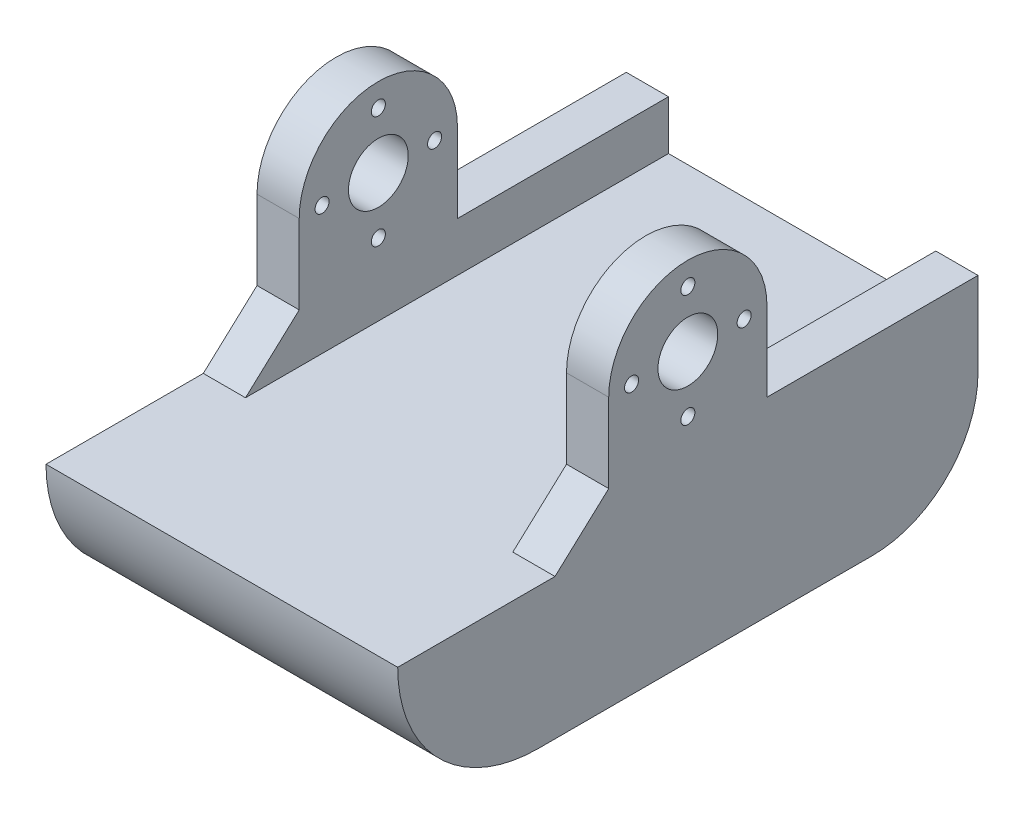
SolidWorks part; units mm, degrees
ref_plane "Front Plane" through (0, 0, 0) normal (0, 0, 1) x (1, 0, 0)
ref_plane "Top Plane" through (0, 0, 0) normal (0, 1, 0) x (1, 0, 0)
ref_plane "Right Plane" through (0, 0, 0) normal (1, 0, 0) x (0, 0, -1)
sketch "Sketch1" plane through (0, 0, 0) normal (0, 0, 1) x (1, 0, 0)
  line L1 (-25, 0) -> (25, 0)
  line L2 (-25, 0) -> (-25, -170)
  line L3 (-25, -170) -> (25, -170)
  line L4 (25, 0) -> (25, -170)
  dimension "D1" = 170
  dimension "D2" = 50
extrude "Boss-Extrude1" add sketch "Sketch1" against normal blind 55
sketch "Sketch2" plane through (0, 0, 0) normal (0, 0, 1) x (1, 0, 0)
  line L0 (25, 0) -> (-25, 0) construction
  line L1 (-17, 0) -> (17, 0)
  line L2 (-17, 0) -> (-17, -27)
  line L3 (-17, -27) -> (17, -27)
  line L4 (17, 0) -> (17, -27)
  line L5 (-25, 0) -> (-25, -170) construction
  dimension "D1" = 8
  dimension "D2" = 34
  dimension "D3" = 27
extrude "Cut-Extrude1" cut sketch "Sketch2" against normal through all
sketch "Sketch3" plane through (25, 0, 0) normal (1, 0, 0) x (0, 0, -1)
  line L0 (0, -170) -> (0, 0) construction
  line L1 (55, -27) -> (0, -27)
  line L2 (55, -27) -> (55, -24)
  line L3 (55, -24) -> (0, -24)
  line L4 (0, -27) -> (0, -24)
  line L5 (55, -170) -> (55, 0) construction
  line L7 (0, 0) -> (10, 0)
  line L8 (0, 0) -> (0, -24)
  line L9 (0, -24) -> (10, -24)
  line L10 (10, 0) -> (10, -24)
  line L11 (55, 0) -> (45, 0)
  line L12 (55, 0) -> (55, -24)
  line L13 (55, -24) -> (45, -24)
  line L14 (45, 0) -> (45, -24)
  circle A0 centre (27.5, -12.75) radius 10.25
  circle A1 centre (27.5, -12.75) radius 4.25
  circle A2 centre (27.5, -12.75) radius 8
  circle A3 centre (27.5, -4.75) radius 1
  circle A4 centre (35.5, -12.75) radius 1
  circle A5 centre (27.5, -20.75) radius 1
  circle A6 centre (19.5, -12.75) radius 1
  point P32 (27.5, -12.75)
  line M7 (0, 0) -> (0, -170)
  line M9 (55, -170) -> (55, 0)
  line M10 (55, 0) -> (0, 0)
  dimension "D2" = 11.25
  dimension "D3" = 27.5
  dimension "D4" = 20.5
  dimension "D7" = 8.5
  dimension "D8" = 16
  dimension "D9" = 4
  dimension "D1" = 3
  dimension "D5" = 10
  dimension "D6" = 10
extrude "Cut-Extrude2" cut sketch "Sketch3" against normal through all contours L14 L3 M10 M9 | L10 L3 M10 M7 | A2 A6 | A2 A6 | A1 | A2 A5 | A2 A5 | A2 A4 | A2 A4 | A2 A3 | A2 A3 region at (25, -12, -50) region at (25, -12, -5) region at (25, -12.75, -27.5) region at (25, -12.75, -35.0645) region at (25, -12.75, -35.913) region at (25, -5.1855, -27.5) region at (25, -4.337, -27.5) region at (25, -21.163, -27.5) region at (25, -20.3145, -27.5) region at (25, -12.75, -19.9355) region at (25, -12.75, -19.087)
sketch "Sketch4" plane through (0, 0, -10) normal (0, 0, 1) x (1, 0, 0)
  line L0 (-25, -24) -> (-17, -24) construction
  line L1 (-17, 0) -> (-19, 0)
  line L2 (-17, 0) -> (-17, -24)
  line L3 (-17, -24) -> (-19, -24)
  line L4 (-19, 0) -> (-19, -24)
  line L5 (0, 0) -> (0, -13.53) construction
  line L6 (19, 0) -> (19, -24)
  line L7 (17, -24) -> (19, -24)
  line L8 (17, 0) -> (17, -24)
  line L9 (17, 0) -> (19, 0)
  dimension "D1" = 2
extrude "Cut-Extrude3" cut sketch "Sketch4" against normal through all
sketch "Sketch5" plane through (25, 0, 0) normal (1, 0, 0) x (0, 0, -1)
  line L1 (10, 0) -> (45, 0)
  line L2 (10, 0) -> (10, -24)
  line L3 (10, -24) -> (45, -24)
  line L4 (45, 0) -> (45, -24)
  line L5 (38.75, -12.75) -> (38.75, -24)
  line L6 (16.25, -12.75) -> (10, -12.75)
  line L7 (16.25, -12.75) -> (16.25, -24)
  line L8 (16.25, -24) -> (10, -24)
  line L9 (10, -12.75) -> (10, -24)
  line L10 (38.75, -12.75) -> (45, -12.75)
  line L11 (38.75, -12.75) -> (38.75, -24)
  line L12 (38.75, -24) -> (45, -24)
  line L13 (45, -12.75) -> (45, -24)
  circle A0 centre (27.5, -12.75) radius 11.25
  line M8 (45, -24) -> (45, 0)
  line M9 (45, 0) -> (10, 0)
  line M10 (10, 0) -> (10, -24)
  dimension "D1" = 22.5
extrude "Cut-Extrude4" cut sketch "Sketch5" against normal through all contours A0 L10 L4 L6 M9 M10 | L7 L6 L2 L3 | L10 L5 L3 M8 region at (25, -0.3725, -27.5) region at (25, -18.375, -13.125) region at (25, -18.375, -41.875)
sketch "Sketch6" plane through (0, 0, 0) normal (0, 0, 1) x (1, 0, 0)
  line L1 (-19, -24) -> (19, -24)
  line L2 (-19, -24) -> (-19, -34)
  line L3 (-19, -34) -> (19, -34)
  line L4 (19, -24) -> (19, -34)
  dimension "D1" = 10
extrude "Cut-Extrude5" cut sketch "Sketch6" against normal through all
sketch "Sketch8" plane through (25, 0, 0) normal (1, 0, 0) x (0, 0, -1)
  line L0 (55, -170) -> (55, -24) construction
  line L1 (0, -170) -> (0, -24) construction
  line L2 (41.75, -132.5) -> (13.25, -132.5)
  line L3 (27.5, -132.5) -> (27.5, -179)
  line L4 (41.75, -179) -> (13.25, -179)
  line L5 (13.25, -132.5) -> (13.25, -179)
  line L7 (41.75, -132.5) -> (41.75, -179)
  line L11 (27.5, -167.75) -> (55, -167.75)
  line L12 (27.5, -167.75) -> (27.5, -170)
  line L13 (27.5, -170) -> (55, -170)
  line L14 (55, -167.75) -> (55, -170)
  line L16 (27.5, -167.75) -> (0, -167.75)
  line L17 (27.5, -167.75) -> (27.5, -170)
  line L18 (27.5, -170) -> (0, -170)
  line L19 (0, -167.75) -> (0, -170)
  circle A0 centre (27.5, -167.75) radius 10.25
  circle A1 centre (27.5, -12.75) radius 10.25
  line M4 (0, -24) -> (0, -170)
  line M5 (0, -170) -> (55, -170)
  line M6 (55, -170) -> (55, -24)
  dimension "D1" = 27.5
  dimension "D2" = 20.5
  dimension "D3" = 155
  dimension "D4" = 14.25
  dimension "D5" = 11.25
  dimension "D6" = 46.5
  dimension "D7" = 13.25
extrude "Cut-Extrude7" cut sketch "Sketch8" against normal through all contours A0 L3 L2 L5 L16 | A0 L11 L7 L2 L3 | L11 L7 M5 M6 | L5 L16 M4 M5 | A0 L16 L5 M5 | A0 L13 L7 L11 | L3 A0 L16 | L11 A0 L3 | L16 A0 L18 L3 | A0 L11 L3 M5 region at (25, -147.5157, -35.1704) region at (25, -147.5157, -19.8296) region at (25, -168.875, -48.375) region at (25, -168.8865, -39.7079) region at (25, -163.3998, -31.8502) region at (25, -163.3998, -23.1498) region at (25, -168.8704, -32.5838) region at (25, -168.8865, -15.2921) region at (25, -168.875, -6.625) region at (25, -168.8704, -22.4162)
sketch "Sketch9" plane through (0, 0, 0) normal (0, 0, 1) x (1, 0, 0)
  line L0 (-25, -167.75) -> (25, -167.75) construction
  line L1 (17, -167.75) -> (-17, -167.75)
  line L2 (17, -167.75) -> (17, -132.5)
  line L3 (17, -132.5) -> (-17, -132.5)
  line L4 (-17, -167.75) -> (-17, -132.5)
  line L5 (-25, -132.5) -> (25, -132.5) construction
  line L7 (-25, -24) -> (-25, -167.75) construction
  line L9 (25, -167.75) -> (25, -24) construction
  dimension "D1" = 8
  dimension "D2" = 8
extrude "Cut-Extrude8" cut sketch "Sketch9" against normal through all
sketch "Sketch11" plane through (25, 0, 0) normal (1, 0, 0) x (0, 0, -1)
  line L0 (27.5, -157.5) -> (27.5, -147.5)
  line L2 (27.5, -147.5) -> (55, -147.5)
  line L3 (27.5, -147.5) -> (27.5, -167.75)
  line L4 (27.5, -167.75) -> (55, -167.75)
  line L5 (55, -147.5) -> (55, -167.75)
  line L6 (27.5, -147.5) -> (0, -147.5)
  line L7 (27.5, -147.5) -> (27.5, -167.75)
  line L8 (27.5, -167.75) -> (0, -167.75)
  line L9 (0, -147.5) -> (0, -167.75)
  circle A0 centre (27.5, -167.75) radius 10.25
  arc A1 (38.75, -12.75) -> (16.25, -12.75) centre (27.5, -12.75) ccw construction
  line M1 (0, -167.75) -> (13.25, -167.75)
  line M2 (13.25, -167.75) -> (13.25, -132.5)
  line M4 (41.75, -132.5) -> (41.75, -167.75)
  line M5 (41.75, -167.75) -> (55, -167.75)
  line M6 (55, -167.75) -> (55, -24)
  line M12 (0, -24) -> (0, -167.75)
  dimension "D1" = 155
  dimension "D2" = 20.5
  dimension "D3" = 10
extrude "Cut-Extrude9" cut sketch "Sketch11" against normal through all contours A0 L0 L6 L8 M2 | A0 L4 L2 L0 M4 | L2 M4 M5 M6 | L6 M2 M12 M1 region at (25, -155.3124, -19.2638) region at (25, -155.3124, -35.7362) region at (25, -157.625, -48.375) region at (25, -157.625, -6.625)
sketch "Sketch12" plane through (25, 0, 0) normal (1, 0, 0) x (0, 0, -1)
  line L1 (13.25, -132.5) -> (41.75, -132.5)
  line L2 (13.25, -132.5) -> (13.25, -147.5)
  line L3 (13.25, -147.5) -> (41.75, -147.5)
  line L4 (41.75, -132.5) -> (41.75, -147.5)
extrude "Boss-Extrude2" add sketch "Sketch12" against normal blind 8
ref_plane "Plane1" through (0, 0, 0) normal (1, 0, 0) x (0, 0, -1)
mirror "Mirror1" about plane through (0, 0, 0) normal (1, 0, 0) of "Boss-Extrude2"
sketch "Sketch14" plane through (0, 0, 0) normal (0, 0, 1) x (1, 0, 0)
  line L0 (17, -148.55) -> (17, -158.75) construction
  line L1 (-17, -132.5) -> (17, -132.5)
  line L2 (-17, -132.5) -> (-17, -147.5)
  line L3 (-17, -147.5) -> (17, -147.5)
  line L4 (17, -132.5) -> (17, -147.5)
  line L5 (-17, -147.5) -> (17, -147.5)
  line L6 (-17, -147.5) -> (-17, -157.75)
  line L7 (-17, -157.75) -> (17, -157.75)
  line L8 (17, -147.5) -> (17, -157.75)
  line M11 (-17, -147.5) -> (-17, -132.5)
  line M12 (-17, -132.5) -> (17, -132.5)
  line M13 (17, -132.5) -> (17, -147.5)
  dimension "D1" = 10.25
extrude "Boss-Extrude3" add sketch "Sketch14" against normal blind 13.25 contours L3 M11 M13 M12 | L8 L3 L6 L7 region at (0, -140, 0) region at (0, -152.625, 0)
ref_plane "Plane2" through (0, 0, -27.5) normal (0, 0, 1) x (1, 0, 0)
mirror "Mirror2" about plane through (0, 0, -27.5) normal (0, 0, 1) of "Boss-Extrude3"
sketch "Sketch16" plane through (25, 0, 0) normal (1, 0, 0) x (0, 0, -1)
  line L0 (41.75, -132.5) -> (13.25, -132.5) construction
  line L1 (13.25, -132.5) -> (13.25, -147.5) construction
  circle A1 centre (16.5, -135.75) radius 2.5
  circle A2 centre (16.5, -135.75) radius 4.5
  circle A3 centre (38.5, -135.75) radius 4.5
  dimension "D1" = 3.25
  dimension "D2" = 3.25
  dimension "D3" = 2
extrude "Cut-Extrude13" cut sketch "Sketch16" against normal blind 8 contours A1 | A2 A1 | A3 region at (25, -135.75, -16.5) region at (25, -135.75, -12.1273) region at (25, -135.75, -38.5)
mirror "Mirror3" about plane through (0, 0, 0) normal (1, 0, 0) of "Cut-Extrude13"
sketch "Sketch17" plane through (25, 0, 0) normal (1, 0, 0) x (0, 0, -1)
  line L0 (55, -147.5) -> (55, -24) construction
  line L1 (27.5, -1.5) -> (55, -1.5)
  line L2 (27.5, -1.5) -> (27.5, -51.5)
  line L3 (27.5, -51.5) -> (55, -51.5)
  line L4 (55, -1.5) -> (55, -51.5)
  line L8 (55, -51.5) -> (0, -51.5)
  line L9 (55, -51.5) -> (55, -157.75)
  line L10 (55, -157.75) -> (0, -157.75)
  line L11 (0, -51.5) -> (0, -157.75)
  arc A0 (38.75, -12.75) -> (16.25, -12.75) centre (27.5, -12.75) ccw construction
  circle M2 centre (16.5, -135.75) radius 4.5
  circle M3 centre (38.5, -135.75) radius 4.5
  line M4 (0, -147.5) -> (55, -147.5)
  line M5 (55, -147.5) -> (55, -24)
  line M11 (0, -24) -> (0, -147.5)
  dimension "D1" = 50
extrude "Cut-Extrude15" cut sketch "Sketch17" against normal through all contours L3 L8 M11 M4 M5 M2 M3 | L11 L10 L9 M4 | M3 | M2 region at (25, -98.6049, -27.5) region at (25, -152.625, -27.5) region at (25, -135.75, -16.5) region at (25, -135.75, -38.5)
sketch "Sketch18" plane through (25, 0, 0) normal (1, 0, 0) x (0, 0, -1)
  line L1 (38.75, -24) -> (-71.25, -24)
  line L2 (38.75, -24) -> (38.75, -51.5)
  line L3 (38.75, -51.5) -> (-71.25, -51.5)
  line L4 (-71.25, -24) -> (-71.25, -51.5)
  line L6 (38.75, -24) -> (68.75, -24)
  line L7 (38.75, -24) -> (38.75, -51.5)
  line L8 (38.75, -51.5) -> (68.75, -51.5)
  line L9 (68.75, -24) -> (68.75, -51.5)
  line M8 (0, -24) -> (0, -51.5)
  line M9 (0, -51.5) -> (55, -51.5)
  line M10 (55, -51.5) -> (55, -24)
  line M11 (55, -24) -> (38.75, -24)
  line M15 (16.25, -24) -> (0, -24)
  dimension "D1" = 110
  dimension "D2" = 30
extrude "Boss-Extrude4" add sketch "Sketch18" against normal blind 50 contours L1 L4 L3 M8 | L9 L6 L8 M10 | L2 L1 M15 M8 M9 | L2 M11 M9 M10 region at (25, -37.75, -19.375) region at (25, -37.75, -46.875) region at (25, -37.75, -61.875) region at (25, -37.75, 35.625)
sketch "Sketch19" plane through (0, 0, 71.25) normal (0, 0, 1) x (1, 0, 0)
  line L1 (-19, -24) -> (19, -24)
  line L2 (-19, -24) -> (-19, -31)
  line L3 (-19, -31) -> (19, -31)
  line L4 (19, -24) -> (19, -31)
  dimension "D1" = 7
extrude "Cut-Extrude16" cut sketch "Sketch19" against normal through all
sketch "Sketch20" plane through (25, 0, 0) normal (1, 0, 0) x (0, 0, -1)
  line L1 (-71.25, -24) -> (68.75, -24)
  line L2 (-71.25, -24) -> (-71.25, -51.5)
  line L3 (-71.25, -51.5) -> (68.75, -51.5)
  line L4 (68.75, -24) -> (68.75, -51.5)
  line L5 (16.25, -24) -> (-13.75, -24)
  line L6 (16.25, -24) -> (16.25, -51.5)
  line L7 (16.25, -51.5) -> (-13.75, -51.5)
  line L8 (-13.75, -24) -> (-13.75, -51.5)
  line L10 (-13.75, -51.5) -> (-71.25, -51.5)
  line L11 (-13.75, -51.5) -> (-13.75, -24)
  line L12 (-13.75, -24) -> (-71.25, -24)
  line L13 (-71.25, -51.5) -> (-71.25, -24)
  line M8 (-71.25, -24) -> (-71.25, -51.5)
  line M9 (-71.25, -51.5) -> (68.75, -51.5)
  dimension "D1" = 30
extrude "Cut-Extrude17" cut sketch "Sketch20" against normal through all contours L8 L1 M8 M9 region at (25, -37.75, 42.5)
sketch "Sketch21" plane through (25, 0, 0) normal (1, 0, 0) x (0, 0, -1)
  line L0 (16.25, -24) -> (-13.75, -51.5)
  line L1 (16.25, -24) -> (-13.75, -24)
  line L2 (16.25, -24) -> (16.25, -51.5)
  line L3 (16.25, -51.5) -> (-13.75, -51.5)
  line L4 (-13.75, -24) -> (-13.75, -51.5)
  line M6 (16.25, -24) -> (-13.75, -24)
  line M7 (-13.75, -24) -> (-13.75, -51.5)
extrude "Cut-Extrude18" cut sketch "Sketch21" against normal through all contours L0 M6 M7 region at (25, -33.1667, 3.75)
sketch "Sketch22" plane through (25, 0, 0) normal (1, 0, 0) x (0, 0, -1)
  line L3 (68.75, -51.5) -> (-13.75, -51.5)
  line L4 (68.75, -51.5) -> (68.75, -54)
  line L5 (68.75, -54) -> (-13.75, -54)
  line L6 (-13.75, -51.5) -> (-13.75, -54)
  dimension "D1" = 2.5
extrude "Boss-Extrude5" add sketch "Sketch22" against normal blind 50
sketch "Sketch24" plane through (25, 0, 0) normal (1, 0, 0) x (0, 0, -1)
  line L1 (68.75, -24) -> (46.75, -24)
  line L2 (68.75, -24) -> (68.75, -41)
  line L3 (68.75, -41) -> (46.75, -41)
  line L4 (46.75, -24) -> (46.75, -41)
  dimension "D1" = 17
  dimension "D2" = 22
extrude "Cut-Extrude19" cut sketch "Sketch24" against normal through all
sketch "Sketch25" plane through (0, -31, 0) normal (0, 1, 0) x (1, 0, 0)
  line L1 (-19, 46.75) -> (19, 46.75)
  line L2 (-19, 46.75) -> (-19, 8.6136)
  line L3 (-19, 8.6136) -> (19, 8.6136)
  line L4 (19, 46.75) -> (19, 8.6136)
extrude "Cut-Extrude20" cut sketch "Sketch25" against normal blind 10
sketch "Sketch26" plane through (25, 0, 0) normal (1, 0, 0) x (0, 0, -1)
  line L1 (-13.75, -51.5) -> (68.75, -51.5)
  line L2 (-13.75, -51.5) -> (-13.75, -54)
  line L3 (-13.75, -54) -> (68.75, -54)
  line L4 (68.75, -51.5) -> (68.75, -54)
extrude "Cut-Extrude21" cut sketch "Sketch26" against normal through all
sketch "Sketch27" plane through (0, 0, -8.6136) normal (0, 0, -1) x (-1, 0, 0)
  line L0 (19, -41) -> (19, -31) construction
  line L1 (-19, -41) -> (19, -41)
  line L2 (-19, -41) -> (-19, -36)
  line L3 (-19, -36) -> (19, -36)
  line L4 (19, -41) -> (19, -36)
extrude "Boss-Extrude6" add sketch "Sketch27" along normal blind 60.14
sketch "Sketch29" plane through (0, 0, -8.6136) normal (0, 0, -1) x (-1, 0, 0)
  line L1 (-19, -31) -> (19, -31)
  line L2 (-19, -31) -> (-19, -36)
  line L3 (-19, -36) -> (19, -36)
  line L4 (19, -31) -> (19, -36)
extrude "Boss-Extrude8" add sketch "Sketch29" along normal blind 60.14
sketch "Sketch30" plane through (0, 0, -46.75) normal (0, 0, -1) x (-1, 0, 0)
  line L1 (-25, -24) -> (-19, -24)
  line L2 (-25, -24) -> (-25, -41)
  line L3 (-25, -41) -> (-19, -41)
  line L4 (-19, -24) -> (-19, -41)
  line L5 (19, -24) -> (25, -24)
  line L6 (19, -24) -> (19, -41)
  line L7 (19, -41) -> (25, -41)
  line L8 (25, -24) -> (25, -41)
extrude "Boss-Extrude9" add sketch "Sketch30" along normal blind 22.14
sketch "Sketch31" plane through (25, 0, 0) normal (1, 0, 0) x (0, 0, -1)
  line L1 (-13.75, -51.5) -> (8.6136, -51.5)
  line L2 (-13.75, -51.5) -> (-13.75, -31)
  line L3 (-13.75, -31) -> (8.6136, -31)
  line L4 (8.6136, -51.5) -> (8.6136, -31)
extrude "Boss-Extrude10" add sketch "Sketch31" against normal blind 50
sketch "Sketch32" plane through (25, 0, 0) normal (1, 0, 0) x (0, 0, -1)
  line L0 (68.75, -41) -> (68.75, -51.5) construction
  line L1 (-13.75, -51.5) -> (68.75, -51.5)
  line L2 (-13.75, -51.5) -> (-13.75, -51)
  line L3 (-13.75, -51) -> (68.75, -51)
  line L4 (68.75, -51.5) -> (68.75, -51)
  line L6 (68.89, -24) -> (68.75, -24)
  line L7 (68.89, -24) -> (68.89, -41)
  line L8 (68.89, -41) -> (68.75, -41)
  line L9 (68.75, -24) -> (68.75, -41)
  dimension "D1" = 0.5
extrude "Cut-Extrude22" cut sketch "Sketch32" against normal through all
fillet "Fillet1" radius 15 1 edges at (0, -51, -68.75)
fillet "Fillet2" radius 20 1 edges at (0, -51, 13.75)
